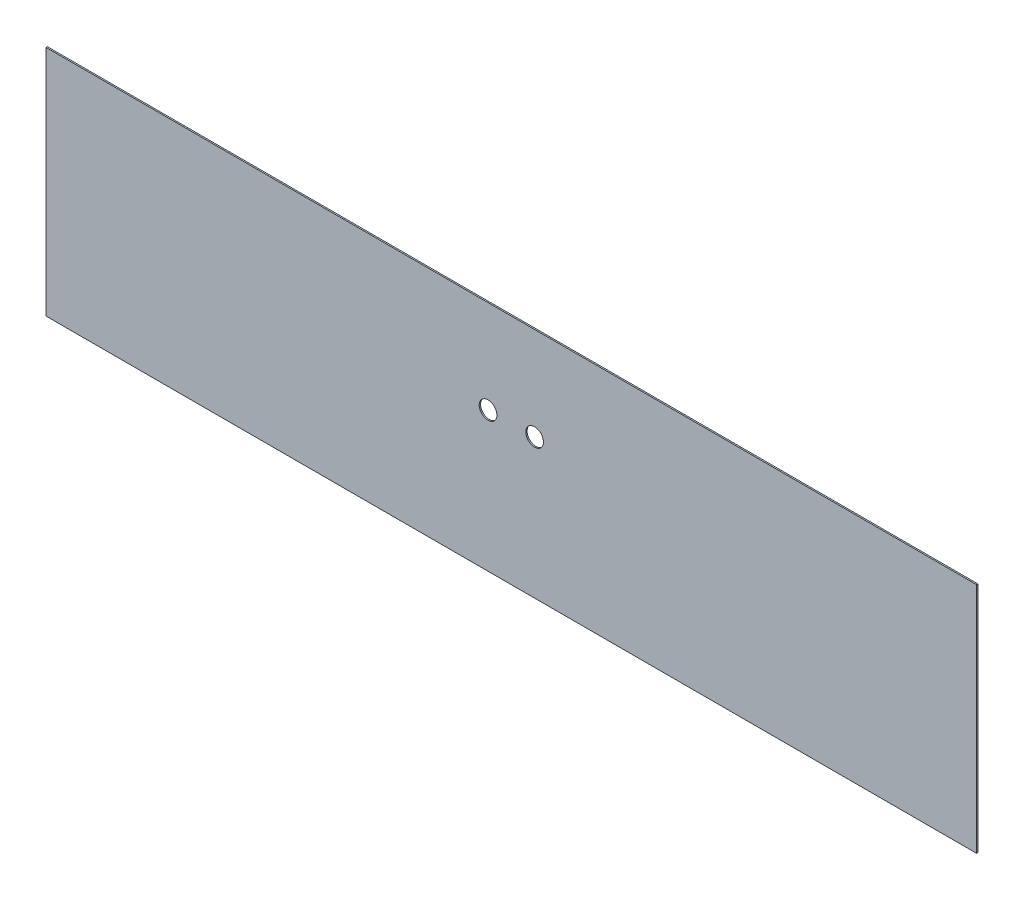
SolidWorks part; units mm, degrees
ref_plane "Front Plane" through (0, 0, 0) normal (0, 0, 1) x (1, 0, 0)
ref_plane "Top Plane" through (0, 0, 0) normal (0, 1, 0) x (1, 0, 0)
ref_plane "Right Plane" through (0, 0, 0) normal (1, 0, 0) x (0, 0, -1)
sketch "Sketch1" plane through (0, 0, 0) normal (0, 0, 1) x (1, 0, 0)
  line L1 (0, 0) -> (508, 0)
  line L2 (0, 0) -> (0, 127)
  line L3 (0, 127) -> (508, 127)
  line L4 (508, 0) -> (508, 127)
  dimension "D1" = 508
  dimension "D2" = 127
base flange "Base-Flange1" sketch "Sketch1" thickness 0.7366 reverse thickness direction no parameters "D1"=12.7
sketch "Sketch2" plane through (0, 0, 0) normal (0, 0, 1) x (1, 0, 0)
  line L0 (254, 127) -> (254, 0) construction
  line L1 (508, 127) -> (0, 127) construction
  line L2 (0, 0) -> (508, 0) construction
  line L3 (229.4897, 76.2) -> (307.8397, 76.2)
  circle A0 centre (266.7, 76.2) radius 4.826
  circle A1 centre (241.3, 76.2) radius 4.826
  dimension "D1" = 9.652
  dimension "D2" = 9.652
  dimension "D3" = 25.4
  dimension "D4" = 12.7
extrude "Cut-Extrude1" cut sketch "Sketch2" against normal blind 2.54 contours A1 | A0 normal cut yes
sketch "Bend-Lines1" [suppressed] plane through (0, 0, 0) normal (0, 1, 0) x (1, 0, 0)
sketch "Bounding-Box1" [suppressed] plane through (0, 0, 0) normal (0, 1, 0) x (1, 0, 0)
sheet metal parameters "Sheet-Metal1" thickness 0.7366 parameters "D1"=12.7
flat pattern "Flat-Pattern1" [suppressed]
sketch "Bend-Lines2" plane through (0, 0, 0) normal (0, 1, 0) x (1, 0, 0)
sketch3d "Bounding-Box2" [suppressed]
  line L0 (0, 0, 0) -> (-508, 0, 0) construction
  line L1 (0, 152.4, 0) -> (-508, 152.4, 0) construction
  line L2 (0, 0, 0) -> (0, 152.4, 0) construction
  line L3 (-508, 0, 0) -> (-508, 152.4, 0) construction
sheet metal parameters "Sheet-Metal2" thickness 0.7366 parameters "D1"=12.7
flat pattern "Flat-Pattern1"
sketch "Bend-Lines2" plane through (0, 0, 0) normal (0, 1, 0) x (1, 0, 0)
sketch3d "Bounding-Box2" [suppressed]
  line L0 (0, 0, 0) -> (508, 0, 0) construction
  line L1 (0, 127, 0) -> (508, 127, 0) construction
  line L2 (0, 0, 0) -> (0, 127, 0) construction
  line L3 (508, 0, 0) -> (508, 127, 0) construction
